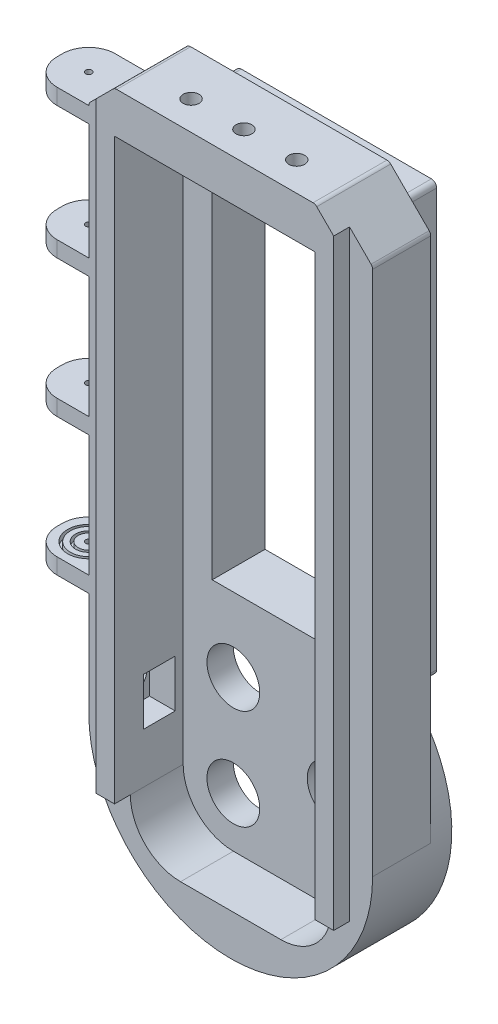
SolidWorks part; units mm, degrees
ref_plane "Alzado" through (0, 0, 0) normal (0, 0, 1) x (1, 0, 0)
ref_plane "Planta" through (0, 0, 0) normal (0, 1, 0) x (1, 0, 0)
ref_plane "Vista lateral" through (0, 0, 0) normal (1, 0, 0) x (0, 0, -1)
sketch "Croquis1" plane through (0, 0, 0) normal (0, 0, 1) x (1, 0, 0)
  line L1 (-19, -40.5) -> (19, -40.5)
  line L2 (-19, -40.5) -> (-19, 40.5)
  line L3 (-19, 40.5) -> (19, 40.5)
  line L4 (19, -40.5) -> (19, 40.5)
  line L5 (-19, -40.5) -> (19, 40.5) construction
  line L6 (-19, 40.5) -> (19, -40.5) construction
  line L7 (-19, -40.5) -> (19, -40.5)
  line L8 (-19, -40.5) -> (-19, -78.5)
  line L9 (-19, -78.5) -> (19, -78.5)
  line L10 (19, -40.5) -> (19, -78.5)
  line L13 (-13.5, 36) -> (13.5, 36)
  line L28 (13.5, 36) -> (13.5, -36)
  line L29 (-13.5, 36) -> (-13.5, -36)
  line L30 (-13.5, -36) -> (13.5, -36)
  circle A0 centre (-9.5, -50) radius 5
  circle A1 centre (9.5, -59.5) radius 5
  circle A2 centre (-9.5, -69) radius 5
  arc A3 (19, -40.5) -> (-19, -40.5) centre (0, -59.5) cw
  point P0 (0, 0)
  point P27 (9.5, -64.5)
  point P30 (9.5, -54.5)
  point P34 (-13.5, 0)
extrude "Saliente-Extruir1" add sketch "Croquis1" along normal blind 5 contours L1 L4 L3 L2 L30 L29 L13 L28 | L10 L1 L8 L9 A2 A1 A0 | A3 L10 | A3 L9 | A3 L8 region at (-18.1053, 0, 0) region at (0.6175, -59.5, 0) region at (-22.1912, -59.5, 0) region at (22.1912, -59.5, 0) region at (0, -81.6912, 0)
sketch "Croquis2" plane through (0, 0, 0) normal (0, 0, -1) x (-1, 0, 0)
  line L0 (-19, 40.5) -> (19, 40.5)
  line L1 (19, -40.5) -> (-19, -40.5)
  line L2 (-19, -40.5) -> (-19, 40.5)
  line L4 (19, -40.5) -> (19, 40.5)
  line L5 (-13.5, 36) -> (-13.5, -36)
  line L7 (-13.5, -36) -> (13.5, -36)
  line L8 (13.5, -36) -> (13.5, 36)
  line L9 (13.5, 36) -> (-13.5, 36)
extrude "Saliente-Extruir2" add sketch "Croquis2" along normal blind 5
sketch "Croquis3" plane through (0, 0, 5) normal (0, 0, 1) x (1, 0, 0)
  line L0 (26.8701, -59.5) -> (26.8701, 40.5)
  line L1 (19, -59.5) -> (19, 40.5)
  line L2 (19, 40.5) -> (-19, 40.5)
  line L3 (-19, 40.5) -> (-19, -59.5)
  line L4 (26.8701, 40.5) -> (19, 48.3701)
  line L5 (19, 48.3701) -> (-19, 48.3701)
  line L6 (-19, 48.3701) -> (-26.8701, 40.5)
  line L7 (-26.8701, 40.5) -> (-26.8701, -59.5)
  arc A2 (-19, -59.5) -> (19, -59.5) centre (0, -59.5) ccw
  arc A3 (-26.8701, -59.5) -> (26.8701, -59.5) centre (0, -59.5) ccw
extrude "Saliente-Extruir9" add sketch "Croquis3" against normal blind 1
sketch "Croquis4" plane through (0, 0, 4) normal (0, 0, -1) x (-1, 0, 0)
  line L0 (-19, 40.5) -> (-19, -40.5)
  line L1 (-19, 40.5) -> (19, 40.5)
  line L2 (19, 40.5) -> (19, -40.5)
  line L3 (14, -77) -> (-14, -77)
  line L4 (-19, -72) -> (-19, -41.338)
  line L5 (19, -72) -> (19, -40.5)
  line L6 (-26.8701, 40.5) -> (-19, 48.3701)
  line L7 (-19, 48.3701) -> (19, 48.3701)
  line L8 (19, 48.3701) -> (26.8701, 40.5)
  line L9 (26.8701, 40.5) -> (26.8701, -59.5)
  line L10 (-26.8701, 40.5) -> (-26.8701, -59.5)
  arc A0 (-19, -40.5) -> (-26.8701, -59.5) centre (0, -59.5) ccw construction
  arc A1 (-14, -77) -> (-19, -72) centre (-14, -72) cw
  arc A2 (14, -77) -> (19, -72) centre (14, -72) ccw
  arc A3 (-19, -40.5) -> (19, -40.5) centre (0, -59.5) ccw construction
  arc A4 (-26.8701, -59.5) -> (26.8701, -59.5) centre (0, -59.5) ccw
  arc M1 (19, -40.5) -> (26.8701, -59.5) centre (0, -59.5) cw
  line M2 (26.8701, -59.5) -> (26.8701, 40.5)
  line M3 (26.8701, 40.5) -> (19, 48.3701)
  line M4 (19, 48.3701) -> (-19, 48.3701)
  line M5 (-19, 48.3701) -> (-26.8701, 40.5)
  line M6 (-26.8701, 40.5) -> (-26.8701, -59.5)
  arc M7 (-26.8701, -59.5) -> (-19, -40.5) centre (0, -59.5) cw
  line M8 (-19, -40.5) -> (-19, 40.5)
  line M9 (-19, 40.5) -> (19, 40.5)
  line M10 (19, 40.5) -> (19, -40.5)
  dimension "D1" = 5
extrude "Saliente-Extruir10" add sketch "Croquis4" against normal blind 11 contours M10 M1 M2 M3 M4 M5 M6 M7 M8 M9 region at (20.2052, 0, 4)
sketch "Croquis5" plane through (0, 0, 5) normal (0, 0, 1) x (1, 0, 0)
  line L0 (-19, -59.5) -> (-19, -69)
  line L1 (19, -69) -> (19, -59.5)
  line L2 (9.5, -78.5) -> (-9.5, -78.5)
  line L3 (19, -59.5) -> (19, -40.5)
  line L4 (-19, -59.5) -> (-19, -40.5)
  arc A0 (-19, -40.5) -> (19, -40.5) centre (0, -59.5) ccw
  arc A1 (-9.5, -78.5) -> (-19, -69) centre (-9.5, -69) cw
  arc A2 (9.5, -78.5) -> (19, -69) centre (9.5, -69) ccw
extrude "Saliente-Extruir11" add sketch "Croquis5" along normal blind 10
fillet "Redondeo1" radius 1 4 edges at (-19, -40.5, -2.5) (-19, 40.5, -0.5) (19, 40.5, -0.5) (19, -40.5, -2.5)
fillet "Redondeo2" radius 1 5 edges at (-18.7071, 40.2071, 4) (18.7071, 40.2071, 4) (-19, -0.5, 4) (0, 40.5, 4) (19, -0.5, 4)
fillet "Redondeo3" radius 1 4 edges at (-26.8701, 40.5, 9.5) (-19, 48.3701, 9.5) (26.8701, 40.5, 9.5) (19, 48.3701, 9.5)
sketch "Croquis6" plane through (-26.8701, 0, 0) normal (-1, 0, 0) x (0, 0, 1)
  line L1 (4, -59.5) -> (15, -59.5) construction
  line L2 (6.5, -50.5) -> (12.5, -50.5)
  line L3 (12.5, -50.5) -> (12.5, -59.5)
  line L4 (12.5, -59.5) -> (6.5, -59.5)
  line L5 (6.5, -50.5) -> (6.5, -59.5)
extrude "Cortar-Extruir1" cut sketch "Croquis6" against normal blind 8
sketch "Croquis7" plane through (-26.8701, 0, 0) normal (-1, 0, 0) x (0, 0, 1)
  line L0 (6.5, -50.5) -> (12.5, -50.5)
  line L1 (12.5, -50.5) -> (12.5, -59.5)
  line L2 (12.5, -59.5) -> (6.5, -59.5)
  line L3 (6.5, -59.5) -> (6.5, -50.5)
  circle A0 centre (9.5, -55) radius 2.5
extrude "Saliente-Extruir12" add sketch "Croquis7" against normal blind 3
sketch "Croquis8" plane through (-26.8701, 0, 0) normal (-1, 0, 0) x (0, 0, 1)
  line L0 (4, 40.0858) -> (4, 37.0858)
  line L1 (4, 39.5) -> (4, -41.5556) construction
  line L2 (4, 37.0858) -> (15, 37.0858)
  line L3 (15, -59.5) -> (15, 40.0858) construction
  line L4 (15, 37.0858) -> (15, 40.0858)
  line L5 (15, 40.0858) -> (4, 40.0858)
  line L6 (9.5, 37.0858) -> (9.5, 15.0858)
  line L7 (9.5, 15.0858) -> (15, 15.0858)
  line L8 (9.5, 15.0858) -> (4, 15.0858)
  line L9 (4, 15.0858) -> (4, 12.0858)
  line L10 (4, 40.0858) -> (4, -59.5) construction
  line L11 (4, 12.0858) -> (15, 12.0858)
  line L12 (15, 12.0858) -> (15, 15.0858)
  line L13 (9.5, 12.0858) -> (9.5, -10.9142)
  line L14 (9.5, -10.9142) -> (15, -10.9142)
  line L15 (15, -10.9142) -> (15, -13.9142)
  line L16 (15, -13.9142) -> (4, -13.9142)
  line L17 (4, -13.9142) -> (4, -10.9142)
  line L18 (4, -10.9142) -> (9.5, -10.9142)
  line L19 (9.5, -13.9142) -> (9.5, -36.9142)
  line L20 (9.5, -36.9142) -> (15, -36.9142)
  line L21 (15, -36.9142) -> (15, -39.9142)
  line L22 (15, -39.9142) -> (4, -39.9142)
  line L23 (4, -39.9142) -> (4, -36.9142)
  line L24 (4, -36.9142) -> (9.5, -36.9142)
  line M2 (15, -59.5) -> (15, 40.0858)
  line M3 (15, 40.0858) -> (4, 40.0858)
  line M4 (4, 40.0858) -> (4, -59.5)
extrude "Saliente-Extruir13" add sketch "Croquis8" along normal blind 11 contours L2 M4 M2 M3 | L11 L7 L8 M4 M2 | L18 L16 L14 M4 M2 | L24 L22 L20 M4 M2 region at (-26.8701, 38.5858, 9.5) region at (-26.8701, 13.5858, 9.5) region at (-26.8701, -12.4142, 9.5) region at (-26.8701, -38.4142, 9.5)
fillet "Redondeo4" radius 5 8 edges at (-37.8701, -38.4142, 4) (-37.8701, -38.4142, 15) (-37.8701, -12.4142, 4) (-37.8701, -12.4142, 15) (-37.8701, 13.5858, 4) (-37.8701, 13.5858, 15) (-37.8701, 38.5858, 4) (-37.8701, 38.5858, 15)
sketch "Croquis9" plane through (0, 40.0858, 0) normal (0, 1, 0) x (1, 0, 0)
  circle A0 centre (-32.3701, -9.5) radius 0.6
extrude "Cortar-Extruir2" cut sketch "Croquis9" against normal blind 80
sketch "Croquis10" plane through (0, -39.9142, 0) normal (0, -1, 0) x (1, 0, 0)
  circle A0 centre (-32.3701, 9.5) radius 0.6
extrude "Saliente-Extruir14" add sketch "Croquis10" against normal blind 2
sketch "Croquis11" plane through (0, -36.9142, 0) normal (0, 1, 0) x (1, 0, 0)
  circle A0 centre (-32.3701, -9.5) radius 2
  circle A1 centre (-32.3701, -9.5) radius 2.5
  circle A2 centre (-32.3701, -9.5) radius 3.5
  circle A3 centre (-32.3701, -9.5) radius 4
extrude "Cortar-Extruir3" cut sketch "Croquis11" against normal blind 1 contours A3 A2 | A1 A0 region at (-34.7993, -36.9142, 9.5) region at (-36.2569, -36.9142, 9.5)
sketch "Croquis13" plane through (0, 0, 15) normal (0, 0, 1) x (1, 0, 0)
  line L0 (19, 40.5) -> (22.5, 40.5)
  line L1 (19, -69) -> (22.5, -69)
  line L2 (22.5, -69) -> (22.5, 40.5)
  line L3 (19, -69) -> (19, 40.5)
  line L5 (22.5, 40.5) -> (22.5, 44.8701)
  line L6 (-19, -69) -> (-19, 40.5)
  line L7 (-22.5, -69) -> (-22.5, 40.5)
  line L8 (-19, -69) -> (-22.5, -69)
  line L9 (-19, 40.5) -> (-22.5, 40.5)
  line L10 (-19, -69) -> (-19, -65.5)
  line L12 (19, -65.5) -> (19, -69)
  line L13 (-22.5, 40.5) -> (-22.5, 44.8701)
  line L14 (-26.5772, 40.7929) -> (-19.2929, 48.0772) construction
  line L15 (-22.5, 44.8701) -> (-19.2929, 48.0772)
  line L16 (-18.5858, 48.3701) -> (18.5858, 48.3701)
  line L19 (22.5, 44.8701) -> (19.2929, 48.0772)
  arc A0 (-19.2929, 48.0772) -> (-18.5858, 48.3701) centre (-18.5858, 47.3701) cw
  arc A1 (19.2929, 48.0772) -> (18.5858, 48.3701) centre (18.5858, 47.3701) ccw
  line M1 (19, 40.5) -> (19, -69)
  line M5 (-19, -69) -> (-19, 40.5)
  line M6 (-19, 40.5) -> (19, 40.5)
  line M14 (26.5772, 40.7929) -> (19.2929, 48.0772)
  arc M15 (19.2929, 48.0772) -> (18.5858, 48.3701) centre (18.5858, 47.3701) ccw
  line M16 (18.5858, 48.3701) -> (-18.5858, 48.3701)
  arc M17 (-18.5858, 48.3701) -> (-19.2929, 48.0772) centre (-18.5858, 47.3701) ccw
  line M18 (-19.2929, 48.0772) -> (-26.5772, 40.7929)
extrude "Saliente-Extruir15" add sketch "Croquis13" along normal blind 3 contours L6 L9 L7 L8 M5 | L1 L2 L0 L3 M1 | L13 L9 L0 L5 M6 M14 M15 M16 M17 M18 region at (0, 44.3353, 15) region at (20.75, -14.25, 15) region at (-20.75, -14.25, 15)
sketch "Croquis15" plane through (0, 48.3701, 0) normal (0, 1, 0) x (1, 0, 0)
  circle A0 centre (0, -12.5) radius 1.5
  circle A1 centre (-10, -12.5) radius 1.5
  circle A2 centre (10, -12.5) radius 1.5
extrude "Cortar-Extruir5" cut sketch "Croquis15" against normal blind 5
